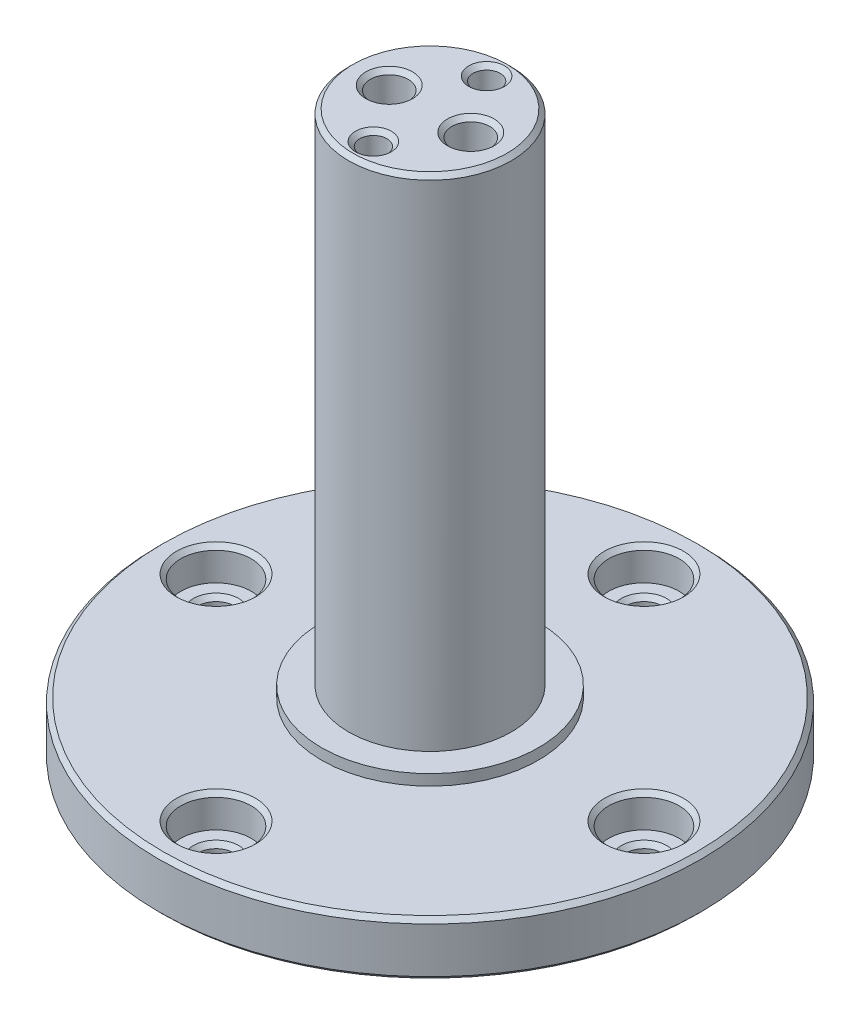
SolidWorks part; units mm, degrees
ref_plane "Front Plane" through (0, 0, 0) normal (0, 0, 1) x (1, 0, 0)
ref_plane "Top Plane" through (0, 0, 0) normal (0, 1, 0) x (1, 0, 0)
ref_plane "Right Plane" through (0, 0, 0) normal (1, 0, 0) x (0, 0, -1)
sketch "Sketch1" plane through (0, 0, 0) normal (0, 0, 1) x (1, 0, 0)
  line L0 (0, 0) -> (25, 0)
  line L1 (10, 5) -> (10, 6)
  line L2 (10, 6) -> (7.5, 6)
  line L3 (7.5, 6) -> (7.5, 52)
  line L4 (7.5, 52) -> (0, 52)
  line L5 (0, 52) -> (0, 0)
  line L6 (10, 5) -> (25, 5)
  line L7 (25, 5) -> (25, 0)
  dimension "D1" = 25
  dimension "D2" = 7.5
  dimension "D3" = 10
  dimension "D4" = 46
  dimension "D5" = 1
  dimension "D6" = 5
revolve "Revolve1" add sketch "Sketch1" angle 360 about L5
sketch "Sketch2" plane through (0, 5, 0) normal (0, 1, 0) x (1, 0, 0)
  line L0 (0, 0) -> (-19.7225, 0)
  dimension "D1" = 19.7225
hole_wizard "CBORE for M3 SHCS1" positions "Sketch3" profile "Sketch4" counterbore size "M3" standard "ANSI Metric" end condition through all
sketch "Sketch3" plane through (0, 5, 0) normal (0, 1, 0) x (1, 0, 0)
  point P0 (-19.7225, 0)
sketch "Sketch4" plane through (-19.7225, 5, 0) normal (1, 0, 0) x (0, 0, 1)
  line L0 (0, 0) -> (0, 5)
  line L1 (1.7, 4.6) -> (2.1, 5)
  line L2 (1.7, 4.6) -> (1.7, 3.4)
  line L3 (1.7, 3.4) -> (2.1, 3)
  line L4 (2.1, 3) -> (3.25, 3)
  line L5 (3.25, 3) -> (3.25, 0.4)
  line L6 (3.25, 0.4) -> (3.65, 0)
  line L7 (3.65, 0) -> (0, 0)
  line L8 (-3.25, 0.4) -> (-3.65, 0) construction
  line L9 (-1.7, 3.4) -> (-2.1, 3) construction
  line L11 (0, -6.35) -> (0, 107.95) construction
  line L12 (2.1, 5) -> (0, 5)
  line L13 (-1.7, 4.6) -> (-2.1, 5) construction
  dimension "Thru Hole Dia." = 3.4
  dimension "Thru Hole Depth" = 5
  dimension "C'Bore Dia." = 6.5
  dimension "C'Bore Depth" = 3
  dimension "Near C'Sink Dia." = 7.3
  dimension "Near C'Sink Angle" = 90
  dimension "Mid C'Sink Dia." = 4.2
  dimension "Mid C'Sink Angle" = 90
  dimension "Far C'Sink Dia." = 4.2
  dimension "Far C'Sink Angle" = 90
pattern_circular "CirPattern1" count 4 over 360 about axis through (0, 52, 0) along (0, 1, 0) of "CBORE for M3 SHCS1" reverse direction yes
sketch "Sketch5" plane through (0, 0, 0) normal (0, -1, 0) x (1, 0, 0)
  line L0 (-3.7592, 0) -> (3.7592, 0) construction
  line L1 (-1.0092, -1.5877) -> (-1.0092, 1.5877)
  line L2 (-1.0092, 1.5877) -> (-3.7592, 3.1754)
  line L3 (-3.7592, 3.1754) -> (-6.5092, 1.5877)
  line L4 (-6.5092, 1.5877) -> (-6.5092, -1.5877)
  line L5 (-6.5092, -1.5877) -> (-3.7592, -3.1754)
  line L6 (-3.7592, -3.1754) -> (-1.0092, -1.5877)
  line L7 (3.7592, 3.1754) -> (1.0092, 1.5877)
  line L8 (1.0092, 1.5877) -> (1.0092, -1.5877)
  line L9 (1.0092, -1.5877) -> (3.7592, -3.1754)
  line L10 (3.7592, -3.1754) -> (6.5092, -1.5877)
  line L11 (6.5092, -1.5877) -> (6.5092, 1.5877)
  line L12 (6.5092, 1.5877) -> (3.7592, 3.1754)
  line L13 (0, 5.2197) -> (0, -5.2197) construction
  circle A0 centre (0, 0) radius 7.5 construction
  circle A1 centre (0, 0) radius 7.5 construction
  circle A2 centre (-3.7592, 0) radius 2.75 construction
  circle A3 centre (3.7592, 0) radius 2.75 construction
  circle A4 centre (0, 5.2197) radius 3.25 construction
  circle A5 centre (0, -5.2197) radius 3.25 construction
  circle A6 centre (0, -5.2197) radius 1.25 construction
  circle A7 centre (0, 5.2197) radius 1.25 construction
  circle A8 centre (0, 5.2197) radius 3.65 construction
  circle A11 centre (-6.5092, 1.5877) radius 0.8 construction
  circle A12 centre (-3.7592, 0) radius 1.75 construction
  circle A13 centre (3.7592, 0) radius 1.75 construction
  dimension "D2" = 0.4
  dimension "D3" = 6.5
  dimension "D4" = 2.5
  dimension "D5" = 1.6
  dimension "D6" = 3.5
  dimension "D1" = 5.5
extrude "Cut-Extrude1" cut sketch "Sketch5" against normal offset from surface (47 mm away) 5 up to face at (0, 52, 7.5)
sketch "Sketch6" plane through (0, 47, 0) normal (0, -1, 0) x (1, 0, 0)
  circle A0 centre (3.7592, 0) radius 1.75 construction
  circle A1 centre (-3.7592, 0) radius 1.75 construction
  circle A2 centre (3.7592, 0) radius 1.75
  circle A3 centre (-3.7592, 0) radius 1.75
extrude "Cut-Extrude2" cut sketch "Sketch6" against normal through all
hole_wizard "CSK for M3 Flat Head Machine Screw1" positions "Sketch7" profile "Sketch8" countersink size "M3" standard "ANSI Metric" end condition through all
sketch "Sketch7" plane through (0, 0, 0) normal (0, -1, 0) x (-1, 0, 0)
  point P0 (0, -5.2197)
  point P3 (0, 5.2197)
sketch "Sketch8" plane through (0, 0, 5.2197) normal (1, 0, 0) x (0, 0, -1)
  line L0 (0, 0) -> (0, 52)
  line L1 (0, 52) -> (1.25, 52)
  line L2 (1.25, 52) -> (1.25, 2)
  line L3 (1.25, 2) -> (3.25, 0)
  line L5 (3.25, 0) -> (0, 0)
  line L6 (-1.25, 2) -> (-3.25, 0) construction
  line L11 (0, -6.35) -> (0, 107.95) construction
  dimension "Thru Hole Dia." = 2.5
  dimension "Thru Hole Depth" = 52
  dimension "Near C'Sink Dia." = 6.5
  dimension "Near C'Sink Angle" = 90
chamfer "Chamfer1" distance 0.4 angle 45 19 edges at (3.7592, 52, -1.75) (-3.7592, 52, -1.75) (0, 52, -6.4697) (0, 52, 3.9697) (0, 52, 7.5) (0, 5, 25) (0, 0, 25) (2.3842, 0, 2.3816) (5.1342, 0, 2.3816) (6.5092, 0, 0) (5.1342, 0, -2.3816) (2.3842, 0, -2.3816) (1.0092, 0, 0) (-6.5092, 0, 0) (-5.1342, 0, 2.3816) (-2.3842, 0, 2.3816) (-1.0092, 0, 0) (-5.1342, 0, -2.3816) (-2.3842, 0, -2.3816)
chamfer "Chamfer2" distance 1.6 angle 45 12 edges at (-5.1342, 47, -2.3816) (-6.5092, 47, 0) (-5.1342, 47, 2.3816) (-2.3842, 47, -2.3816) (-2.3842, 47, 2.3816) (-1.0092, 47, 0) (1.0092, 47, 0) (2.3842, 47, 2.3816) (5.1342, 47, 2.3816) (6.5092, 47, 0) (5.1342, 47, -2.3816) (2.3842, 47, -2.3816)
